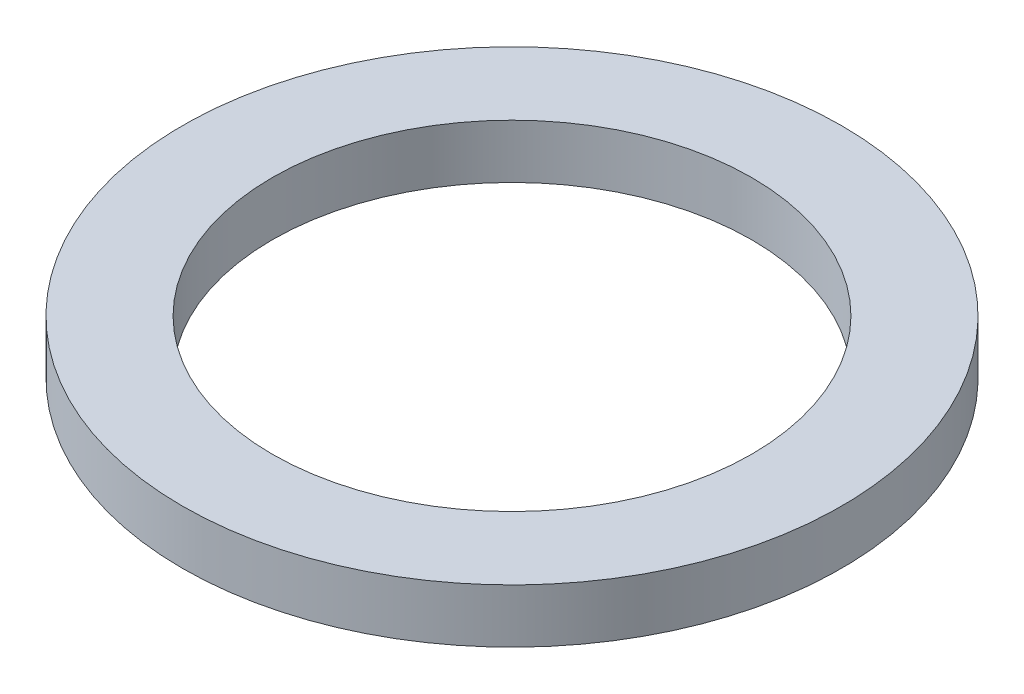
SolidWorks part; units mm, degrees
ref_plane "Front Plane" through (0, 0, 0) normal (0, 0, 1) x (1, 0, 0)
ref_plane "Top Plane" through (0, 0, 0) normal (0, 1, 0) x (1, 0, 0)
ref_plane "Right Plane" through (0, 0, 0) normal (1, 0, 0) x (0, 0, -1)
sketch "Sketch1" plane through (0, 0, 0) normal (0, 1, 0) x (1, 0, 0)
  circle A0 centre (0, 0) radius 55
  dimension "FLANGE_OD" = 110
extrude "Boss-Extrude1" add sketch "Sketch1" along normal blind 9
sketch "Sketch2" plane through (0, 0, 0) normal (0, 1, 0) x (1, 0, 0)
  circle A0 centre (0, 0) radius 40
  dimension "BORE_D" = 80
extrude "Cut-Extrude1" cut sketch "Sketch2" along normal through all
sketch "Sketch3" plane through (0, 9, 0) normal (0, 1, 0) x (1, 0, 0)
  circle A0 centre (0, 0) radius 22.6685 construction
  circle A1 centre (-22.6685, 0) radius 2.5657
  dimension "BOLT_D" = 5.1314
  dimension "BOLT_PCD" = 45.3371
extrude "Cut-Extrude2" cut sketch "Sketch3" against normal blind 7.4994 rebuild error yes
pattern_circular "CirPattern1" count 6 over 360 rebuild error yes
